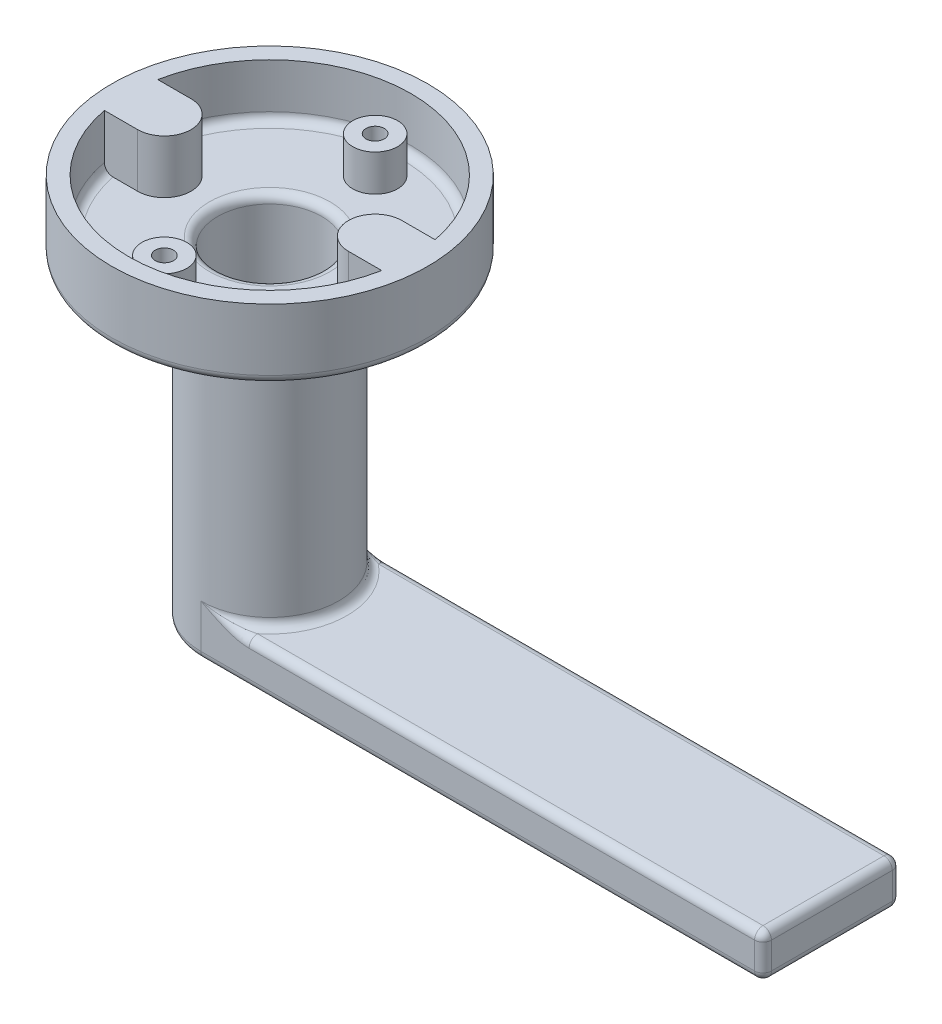
SolidWorks part; units mm, degrees
material "Custom Plastic"
ref_plane "Front Plane" through (0, 0, 0) normal (0, 0, 1) x (1, 0, 0)
ref_plane "Top Plane" through (0, 0, 0) normal (0, 1, 0) x (1, 0, 0)
ref_plane "Right Plane" through (0, 0, 0) normal (1, 0, 0) x (0, 0, -1)
sketch "Sketch1" plane through (0, 0, 0) normal (0, 0, 1) x (1, 0, 0)
  line L0 (-5.8443, 25.9927) -> (-2.7963, 25.9927)
  line L1 (-2.7963, 25.9927) -> (-2.7963, 14.8167)
  line L2 (-4.3203, 13.2927) -> (-17.4013, 13.2927)
  line L3 (-18.9253, 11.7687) -> (-18.9253, -35.9833)
  line L4 (-18.9253, -35.9833) -> (-21.9733, -35.9833)
  line L5 (-21.9733, -35.9833) -> (-21.9733, 5.842)
  line L6 (-21.9733, 5.842) -> (-21.9733, 14.8167)
  line L7 (-20.4493, 16.3407) -> (-7.3683, 16.3407)
  line L8 (-5.8443, 17.8647) -> (-5.8443, 25.9927)
  line L9 (-31.3713, -35.9833) -> (-31.3713, 32.3883) construction
  arc A0 (-17.4013, 13.2927) -> (-18.9253, 11.7687) centre (-17.4013, 11.7687) ccw
  arc A1 (-21.9733, 14.8167) -> (-20.4493, 16.3407) centre (-20.4493, 14.8167) cw
  arc A2 (-7.3683, 16.3407) -> (-5.8443, 17.8647) centre (-7.3683, 17.8647) ccw
  arc A3 (-2.7963, 14.8167) -> (-4.3203, 13.2927) centre (-4.3203, 14.8167) cw
  dimension "D8" = 1.524
  dimension "D1" = 3.048
  dimension "D2" = 3.048
  dimension "D3" = 3.048
  dimension "D4" = 12.7
  dimension "D5" = 61.976
  dimension "D6" = 12.446
  dimension "D7" = 28.575
revolve "Revolve1" add sketch "Sketch1" angle 360 about L9
sketch "Sketch2" plane through (0, 25.9927, 0) normal (0, 1, 0) x (1, 0, 0)
  line L0 (-12.3213, -4.826) -> (-6.3047, -4.826)
  line L1 (-12.3213, 4.826) -> (-6.3047, 4.826)
  line L2 (-50.4213, 4.826) -> (-56.438, 4.826)
  line L3 (-50.4213, -4.826) -> (-56.438, -4.826)
  circle A0 centre (-31.3713, 0) radius 19.05 construction
  arc A1 (-12.3213, 4.826) -> (-12.3213, -4.826) centre (-12.3213, 0) ccw
  circle A4 centre (-31.3713, 19.05) radius 4.064
  circle A5 centre (-31.3713, 0) radius 25.527 construction
  arc A6 (-6.3047, -4.826) -> (-6.3047, 4.826) centre (-31.3713, 0) ccw
  circle A7 centre (-31.3713, 19.05) radius 1.651
  arc A8 (-50.4213, -4.826) -> (-50.4213, 4.826) centre (-50.4213, 0) ccw
  arc A9 (-56.438, 4.826) -> (-56.438, -4.826) centre (-31.3713, 0) ccw
  circle A10 centre (-31.3713, -19.05) radius 1.651
  circle A11 centre (-31.3713, -19.05) radius 4.064
  point P21 (-31.3713, 0)
  point P25 (-31.3713, 0)
  dimension "D1" = 38.1
  dimension "D2" = 9.652
  dimension "D3" = 8.128
  dimension "D4" = 3.302
  dimension "D5" = 2
  dimension "D6" = 2
extrude "Boss-Extrude1" add sketch "Sketch2" against normal up to body separate body
sketch "Sketch3" plane through (0, -35.9833, 0) normal (0, -1, 0) x (1, 0, 0)
  line L1 (-31.3713, -12.446) -> (68.7047, -12.446)
  line L2 (-31.3713, 12.446) -> (68.7047, 12.446)
  line L3 (70.2287, -10.922) -> (70.2287, 10.922)
  arc A0 (-31.3713, 12.446) -> (-31.3713, -12.446) centre (-31.3713, 0) ccw
  arc A1 (68.7047, 12.446) -> (70.2287, 10.922) centre (68.7047, 10.922) cw
  arc A2 (68.7047, -12.446) -> (70.2287, -10.922) centre (68.7047, -10.922) ccw
  point P6 (70.2287, 12.446)
  point P11 (70.2287, -12.446)
  dimension "D3" = 1.524
  dimension "D1" = 101.6
  dimension "D2" = 24.892
extrude "Boss-Extrude2" add sketch "Sketch3" along normal blind 7.874
fillet "Fillet1" radius 1.524 1 edges at (-31.3713, -35.9833, -9.398)
fillet "Fillet2" radius 1.524 1 edges at (-18.9253, -35.9833, 0)
sketch "Sketch5" plane through (0, 25.9927, 0) normal (0, 1, 0) x (1, 0, 0)
  circle A0 centre (-31.3713, -19.05) radius 4.064
  circle A1 centre (-31.3713, 19.05) radius 4.064
extrude "Cut-Extrude1" cut sketch "Sketch5" against normal blind 3.048 contours A0 | A1
fillet "Fillet3" radius 1.524 13 edges at (-43.8173, -43.8573, 0) (18.6667, -43.8573, 12.446) (69.7823, -43.8573, 11.9996) (70.2287, -43.8573, 0) (69.7823, -43.8573, -11.9996) (-28.0744, -35.5196, 12.446) (21.8391, -35.9833, 12.446) (69.7823, -35.9833, 11.9996) (70.2287, -35.9833, 0) (69.7823, -35.9833, -11.9996) (18.6667, -43.8573, -12.446) (21.8391, -35.9833, -12.446) (-28.0744, -35.5196, -12.446)
